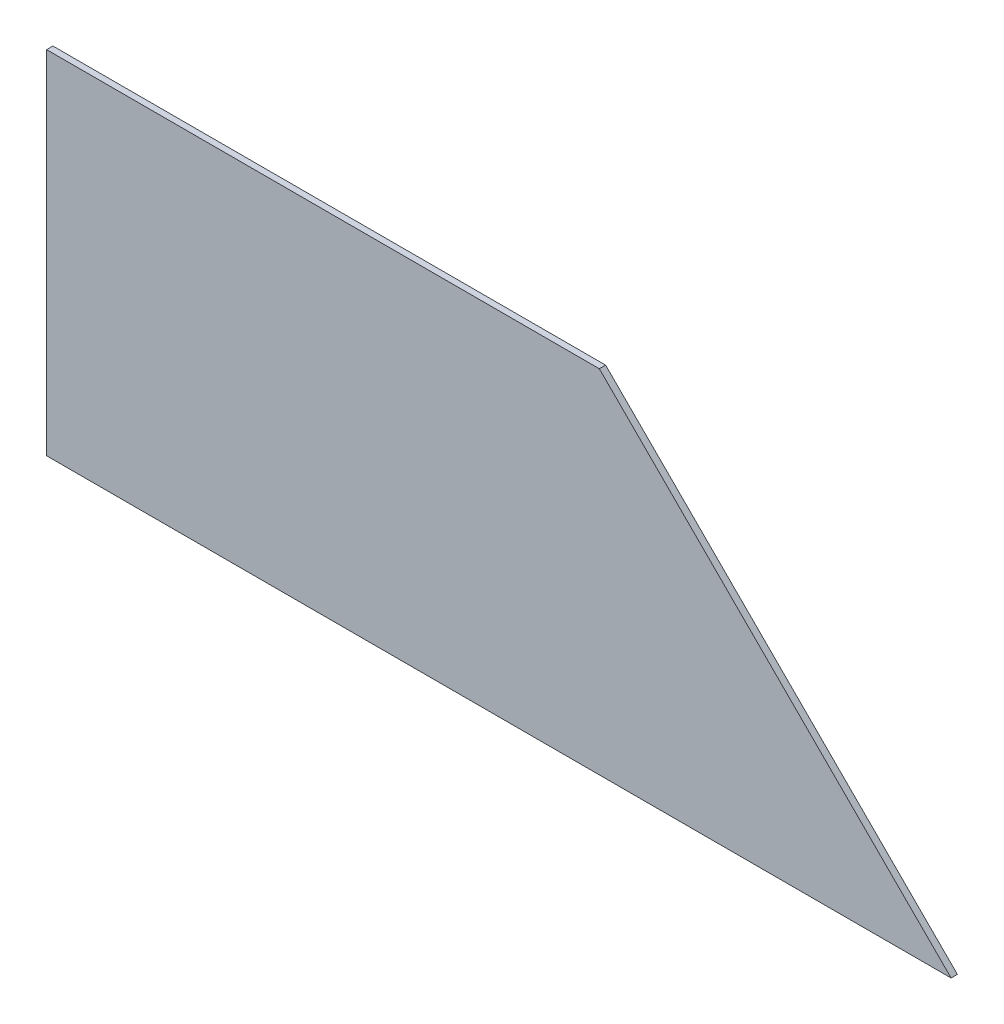
SolidWorks part; units mm, degrees
ref_plane "Front Plane" through (0, 0, 0) normal (0, 0, 1) x (1, 0, 0)
ref_plane "Top Plane" through (0, 0, 0) normal (0, 1, 0) x (1, 0, 0)
ref_plane "Right Plane" through (0, 0, 0) normal (1, 0, 0) x (0, 0, -1)
sketch "Sketch1" plane through (0, 0, 0) normal (0, 0, 1) x (1, 0, 0)
  line L0 (279.4, 177.8) -> (457.2, 0)
  line L1 (0, 0) -> (127, 0)
  line L2 (0, 0) -> (0, 177.8)
  line L3 (0, 177.8) -> (279.4, 177.8)
  line L5 (457.2, 0) -> (127, 0)
  dimension "D1" = 279.4
  dimension "D2" = 177.8
  dimension "D3" = 45
extrude "Boss-Extrude1" add sketch "Sketch1" along normal blind 3.175
